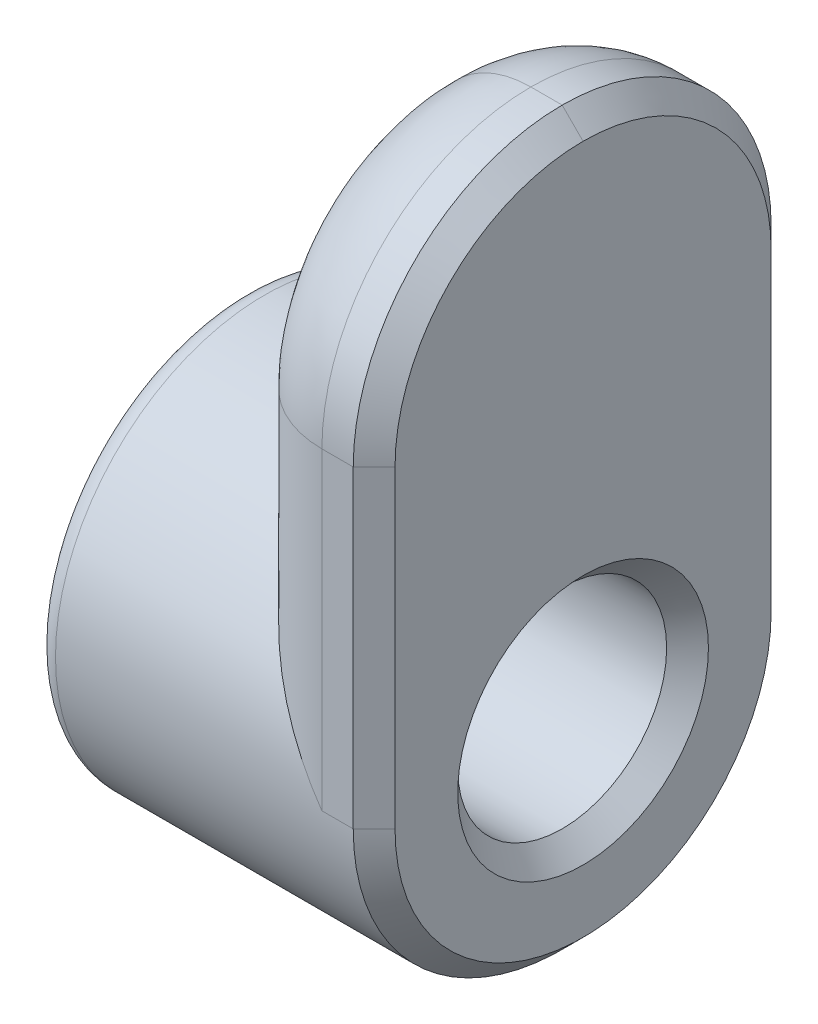
SolidWorks part; units mm, degrees
ref_plane "前视基准面" through (0, 0, 0) normal (0, 0, 1) x (1, 0, 0)
ref_plane "上视基准面" through (0, 0, 0) normal (0, 1, 0) x (1, 0, 0)
ref_plane "右视基准面" through (0, 0, 0) normal (1, 0, 0) x (0, 0, -1)
other "Configuration Table"
sketch "草图1" plane through (0, 0, 0) normal (1, 0, 0) x (0, 0, -1)
  circle A0 centre (0, 0) radius 2
  circle A1 centre (0, 0) radius 4
  point P4 (0, 0)
  dimension "D1" = 4
  dimension "D2" = 8
extrude "凸台-拉伸1" add sketch "草图1" along normal blind 6.5
sketch "草图2" plane through (6.5, 0, 0) normal (1, 0, 0) x (0, 0, -1)
  line L0 (2, 0) -> (4, 0)
  line L1 (-4, 0) -> (-2, 0)
  line L2 (-4, 0) -> (-4, 10)
  line L3 (-4, 10) -> (4, 10)
  line L4 (4, 0) -> (4, 10)
  circle A0 centre (0, 0) radius 4 construction
  arc A1 (2, 0) -> (-2, 0) centre (0, 0) ccw
  dimension "D1" = 10
extrude "凸台-拉伸2" add sketch "草图2" against normal blind 3
fillet "圆角1" radius 4 2 edges at (5, 10, -4) (5, 10, 4)
chamfer "倒角1" distance 0.4 angle 45 6 edges at (6.5, 0, -2) (6.5, -4, 0) (6.5, 3, 4) (6.5, 8.8284, 2.8284) (6.5, 8.8284, -2.8284) (6.5, 3, -4)
fillet "圆角2" radius 2 4 edges at (3.5, 3, 4) (3.5, 8.8284, 2.8284) (3.5, 8.8284, -2.8284) (3.5, 3, -4)
fillet "圆角3" radius 0.4 2 edges at (0, 0, -2) (0, 0, -4)
